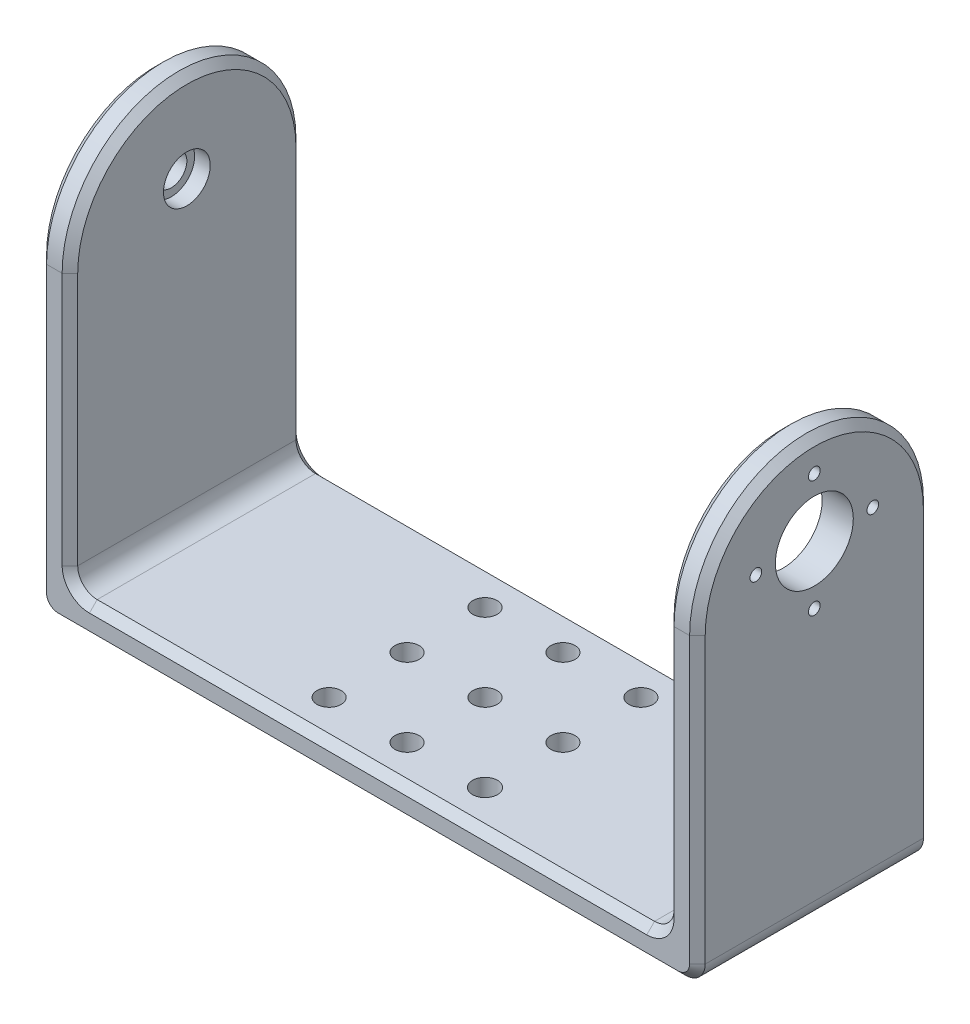
SolidWorks part; units mm, degrees
ref_plane "Front Plane" through (0, 0, 0) normal (0, 0, 1) x (1, 0, 0)
ref_plane "Top Plane" through (0, 0, 0) normal (0, 1, 0) x (1, 0, 0)
ref_plane "Right Plane" through (0, 0, 0) normal (1, 0, 0) x (0, 0, -1)
sketch "Sketch1" plane through (0, 0, 0) normal (0, 1, 0) x (1, 0, 0)
  line L1 (-84.5, 30) -> (84.5, 30)
  line L2 (-84.5, 30) -> (-84.5, -30)
  line L3 (-84.5, -30) -> (84.5, -30)
  line L4 (84.5, 30) -> (84.5, -30)
  point P4 (0, 0)
  point P5 (0, 0)
  point P6 (0, 0)
  point P7 (0, 0)
extrude "Boss-Extrude1" add sketch "Sketch1" along normal blind 8
sketch "Sketch2" plane through (0, 8, 0) normal (0, 1, 0) x (1, 0, 0)
  line L1 (-84.5, 30) -> (-76.5, 30)
  line L2 (-84.5, 30) -> (-84.5, -30)
  line L3 (-84.5, -30) -> (-76.5, -30)
  line L4 (-76.5, 30) -> (-76.5, -30)
  line L5 (76.5, 30) -> (76.5, -30)
  line L6 (84.5, -30) -> (76.5, -30)
  line L7 (84.5, 30) -> (84.5, -30)
  line L8 (84.5, 30) -> (76.5, 30)
  point P4 (0, 0)
  point P8 (0, 0)
  point P9 (0, 0)
  point P11 (0, 0)
  point P12 (0, 0)
  point P13 (0, 0)
  point P14 (0, 0)
  point P15 (0, 0)
extrude "Boss-Extrude2" add sketch "Sketch2" along normal blind 100
sketch "Sketch3" plane through (84.5, 0, 0) normal (1, 0, 0) x (0, 0, -1)
  circle A0 centre (0, 85) radius 10
  circle A3 centre (0, 70) radius 1.5
  circle A4 centre (0, 100) radius 1.5
  circle A5 centre (-15, 85) radius 1.5
  circle A6 centre (15, 85) radius 1.5
sketch "Sketch4" plane through (-84.5, 0, 0) normal (-1, 0, 0) x (0, 0, 1)
  circle A0 centre (0, 85) radius 4
extrude "Cut-Extrude1" cut sketch "Sketch3" against normal blind 12
sketch "Sketch5" plane through (-84.5, 0, 0) normal (-1, 0, 0) x (0, 0, 1)
  circle A0 centre (0, 85) radius 5
extrude "Boss-Extrude3" add sketch "Sketch5" along normal blind 1.5
sketch "Sketch6" plane through (-86, 0, 0) normal (-1, 0, 0) x (0, 0, 1)
  circle A0 centre (0, 85) radius 4
extrude "Cut-Extrude3" cut sketch "Sketch6" against normal blind 15
sketch "Sketch7" plane through (-76.5, 0, 0) normal (1, 0, 0) x (0, 0, -1)
  circle A0 centre (0, 85) radius 6
extrude "Cut-Extrude4" cut sketch "Sketch7" against normal blind 4
fillet "Fillet1" 2 edges at (80.5, 108, -30) (80.5, 108, 30) type full round first side face at (0, 56, -30) second side face at (0, 56, 30) middle face at (80.5, 108, 0)
fillet "Fillet2" 2 edges at (-80.5, 108, -30) (-80.5, 108, 30) type full round first side face at (0, 48.5, -30) second side face at (0, 48.5, 30) middle face at (-80.5, 108, 0)
fillet "Fillet3" radius 5 1 edges at (76.5, 8, 0) type face fillet first side face at (76.5, 70, -1.5) second side face at (0, 8, 0)
fillet "Fillet4" radius 5 1 edges at (-76.5, 8, 0) type face fillet first side face at (-76.5, 85, -6) second side face at (-2.5, 8, 0)
fillet "Fillet5" radius 5 1 edges at (84.5, 0, 0) type face fillet first side face at (84.5, 70, -1.5) second side face at (0, 0, 0)
fillet "Fillet6" radius 5 1 edges at (-84.5, 0, 0) type face fillet first side face at (-84.5, 85, -5) second side face at (-2.5, 0, 0)
fillet "Chamfer1" radius 2 24 edges at (84.5, 108, 0) (76.5, 108, 0) (-76.5, 108, 0) (-84.5, 108, 0) (83.0355, 1.4645, -30) (84.5, 41.5, -30) (76.5, 45.5, -30) (75.0355, 9.4645, -30) (0, 8, -30) (-75.0355, 9.4645, -30) (-76.5, 45.5, -30) (-84.5, 41.5, -30) (-83.0355, 1.4645, -30) (-76.5, 45.5, 30) (-75.0355, 9.4645, 30) (0, 8, 30) (75.0355, 9.4645, 30) (76.5, 45.5, 30) (84.5, 41.5, 30) (83.0355, 1.4645, 30) (-83.0355, 1.4645, 30) (-84.5, 41.5, 30) (0, 0, -30) (0, 0, 30) profile chamfer
sketch "Sketch8" plane through (0, 8, 0) normal (0, 1, 0) x (1, 0, 0)
  circle A0 centre (0, 0) radius 3.1
  circle A1 centre (0, 20) radius 3.1
  circle A2 centre (0, -20) radius 3.1
  circle A3 centre (-20, -20) radius 3.1
  circle A4 centre (-20, 20) radius 3.1
  circle A5 centre (-20, 0) radius 3.1
  circle A6 centre (20, -20) radius 3.2
  circle A7 centre (20, 0) radius 3.1
  circle A8 centre (20, 20) radius 3.1
extrude "Cut-Extrude5" cut sketch "Sketch8" against normal blind 10
